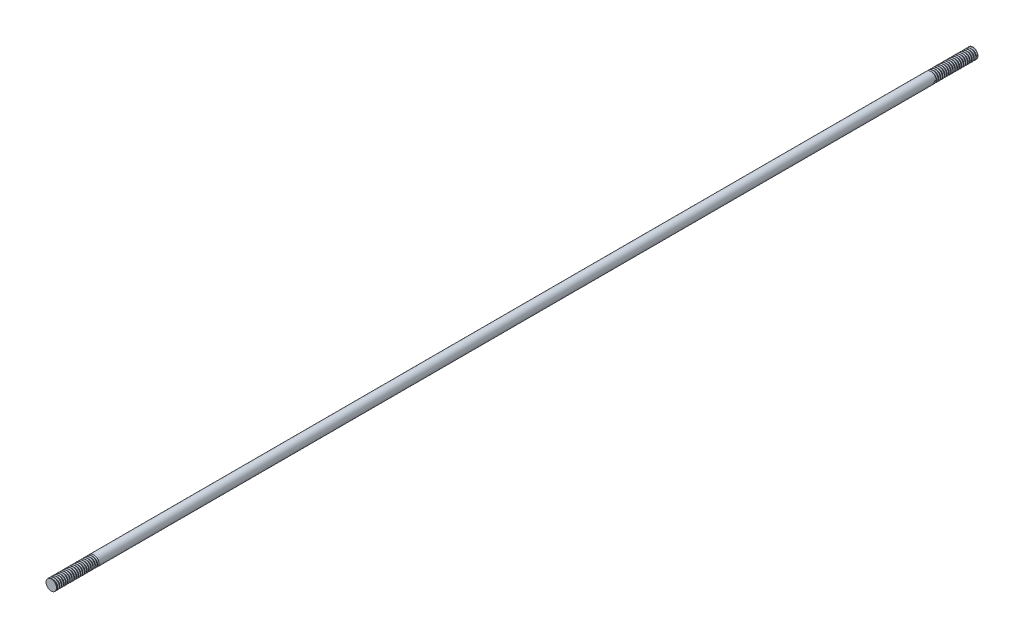
SolidWorks part; units mm, degrees
ref_plane "Front Plane" through (0, 0, 0) normal (0, 0, 1) x (1, 0, 0)
ref_plane "Top Plane" through (0, 0, 0) normal (0, 1, 0) x (1, 0, 0)
ref_plane "Right Plane" through (0, 0, 0) normal (1, 0, 0) x (0, 0, -1)
sketch "Sketch1" plane through (0, 0, 0) normal (0, 0, 1) x (1, 0, 0)
  circle A0 centre (0, 0) radius 3.175
  dimension "D1" = 6.35
extrude "Boss-Extrude1" add sketch "Sketch1" along normal blind 558.3149
thread "Thread2" pitch 1.27 method cut profile "Thread Profile1" start angle 2, offset 0, length 25.4, pitch 1.27, diameter 6.35
ref_plane "Plane1" through (3.1731, 0.1108, 0) normal (0.0349, -0.9994, 0) x (0.9994, 0.0349, 0)
sketch "Thread Profile1" plane through (3.1731, 0.1108, 0) normal (0.0349, -0.9994, 0) x (0.9994, 0.0349, 0)
  line L0 (0, 0) -> (0, 1.27) construction
  line L11 (0, 0) -> (0, 1.1112)
  line L12 (0, 1.1112) -> (-0.6874, 0.7144)
  line L13 (-0.6874, 0.7144) -> (-0.6874, 0.3969)
  line L15 (-0.6874, 0.3969) -> (0, 0)
  line L17 (-0.6874, 0.5556) -> (0, 0.5556) construction
  point P2 (0, 0)
  dimension "Pitch" = 1.27
  dimension "Profile_Angle" = 60
  dimension "Profile_Land" = 0.3175
  dimension "Profile_Height" = 0.6874
thread "Thread3" pitch 1.27 method cut profile "Thread Profile2" start angle 2, offset 0, length 25.4, pitch 1.27, diameter 6.35
ref_plane "Plane2" through (-3.1731, 0.1108, 558.3149) normal (-0.0349, -0.9994, 0) x (-0.9994, 0.0349, 0)
sketch "Thread Profile2" plane through (-3.1731, 0.1108, 558.3149) normal (-0.0349, -0.9994, 0) x (-0.9994, 0.0349, 0)
  line L0 (0, 0) -> (0, 1.27) construction
  line L11 (0, 0) -> (0, 1.1112)
  line L12 (0, 1.1112) -> (-0.6874, 0.7144)
  line L13 (-0.6874, 0.7144) -> (-0.6874, 0.3969)
  line L15 (-0.6874, 0.3969) -> (0, 0)
  line L17 (-0.6874, 0.5556) -> (0, 0.5556) construction
  point P2 (0, 0)
  dimension "Pitch" = 1.27
  dimension "Profile_Angle" = 60
  dimension "Profile_Land" = 0.3175
  dimension "Profile_Height" = 0.6874
ref_axis "Axis1" through (0, 0, 558.3149) along (0, 0, -1)
